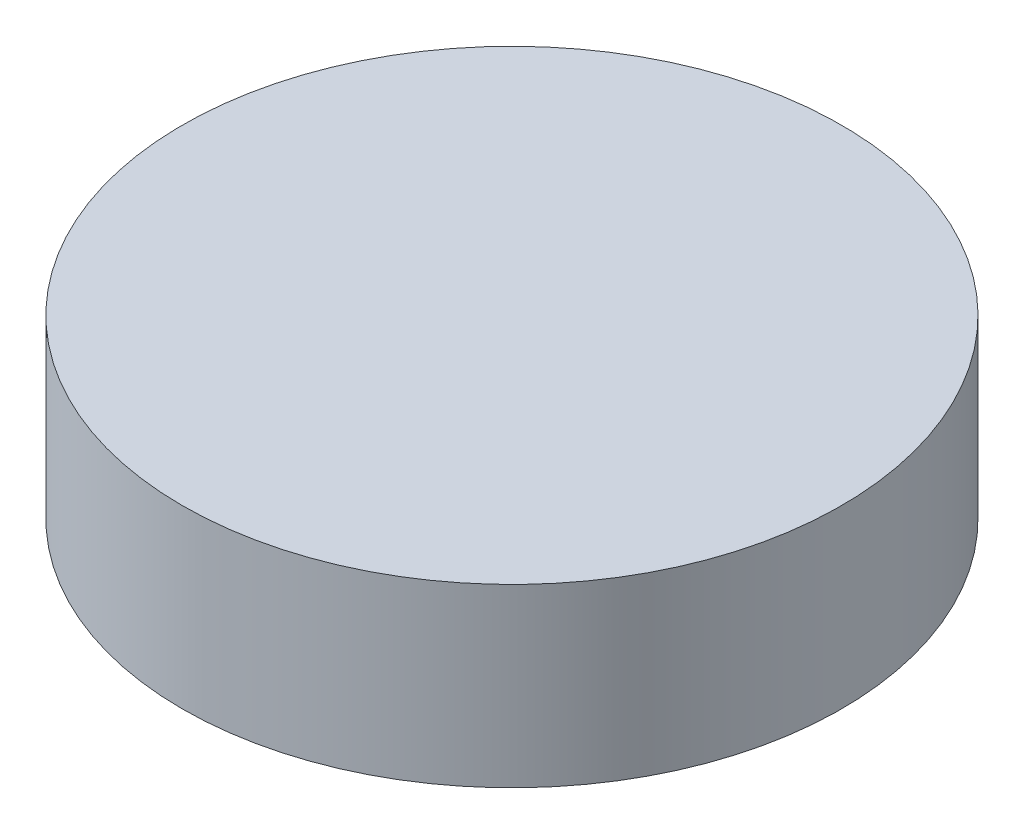
SolidWorks part; units mm, degrees
material "6061-T6 (SS)"
ref_plane "Front Plane" through (0, 0, 0) normal (0, 0, 1) x (1, 0, 0)
ref_plane "Top Plane" through (0, 0, 0) normal (0, 1, 0) x (1, 0, 0)
ref_plane "Right Plane" through (0, 0, 0) normal (1, 0, 0) x (0, 0, -1)
sketch "Sketch1" plane through (0, 0, 0) normal (0, 1, 0) x (1, 0, 0)
  circle A0 centre (0, 0) radius 28.194
  dimension "D1" = 56.388
extrude "Boss-Extrude1" add sketch "Sketch1" along normal blind 12.7
shell "Shell2" thickness 5.08 removed face at (0, 0, 28.194) outward yes
thread "Thread1" pitch 6.35 method cut profile "Thread Profile1" start angle 0, offset 0, length 13.97, pitch 6.35, diameter 56.388
ref_plane "Plane1" through (-28.194, 12.7, 0) normal (0, 0, 1) x (-1, 0, 0)
sketch "Thread Profile1" plane through (-28.194, 12.7, 0) normal (0, 0, 1) x (-1, 0, 0)
  line L0 (0, 0) -> (0, 6.35) construction
  line L1 (0, 0) -> (3.437, 1.9844)
  line L2 (3.437, 1.9844) -> (3.437, 2.7781)
  line L3 (3.437, 2.7781) -> (0, 4.7625)
  line L4 (3.437, 2.3812) -> (0, 2.3812) construction
  line L11 (0, 0) -> (0, 4.7625)
  point P2 (0, 0)
  dimension "Pitch" = 6.35
  dimension "Profile_Angle" = 60
  dimension "Profile_Land" = 0.7937
  dimension "Profile_Height" = 3.437
sketch "Sketch4" plane through (0, 0, 0) normal (1, 0, 0) x (0, 0, -1)
  line L4 (19.939, 9.5281) -> (19.939, 13.0841)
  line L5 (19.939, 13.0841) -> (24.13, 13.0841)
  line L6 (24.13, 13.0841) -> (24.13, 17.7282)
  line L7 (24.13, 17.7282) -> (0, 17.7282)
  line L8 (0, 17.7282) -> (0, 9.5281)
  line L9 (0, 9.5281) -> (19.939, 9.5281)
  dimension "D1" = 24.13
  dimension "D4" = 3.556
revolve "Revolve1" add sketch "Sketch4" angle 360 about L8
